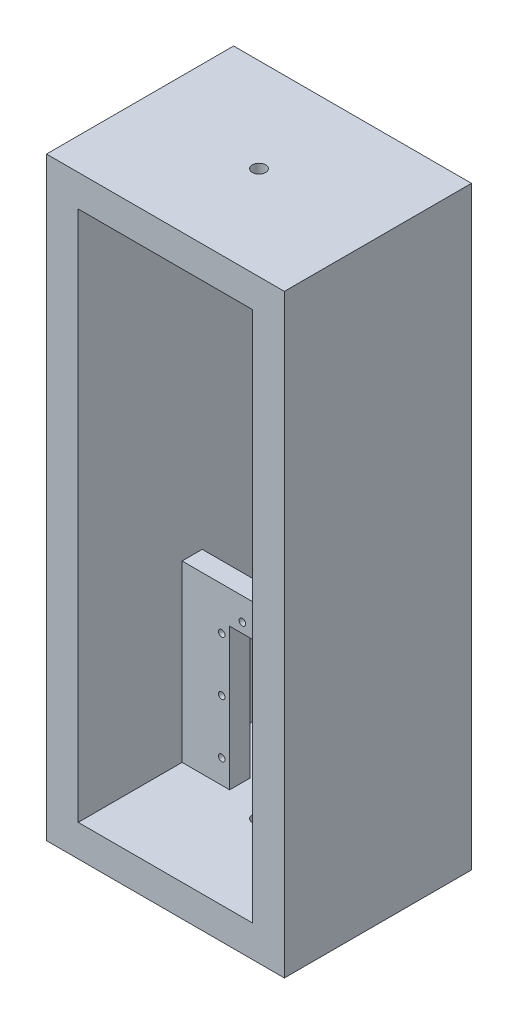
SolidWorks part; units mm, degrees
ref_plane "Front Plane" through (0, 0, 0) normal (0, 0, 1) x (1, 0, 0)
ref_plane "Top Plane" through (0, 0, 0) normal (0, 1, 0) x (1, 0, 0)
ref_plane "Right Plane" through (0, 0, 0) normal (1, 0, 0) x (0, 0, -1)
sketch "Sketch1" plane through (0, 0, 0) normal (0, 0, 1) x (1, 0, 0)
  line L1 (0, 0) -> (75, 0)
  line L2 (0, 0) -> (0, 187.5)
  line L3 (0, 187.5) -> (75, 187.5)
  line L4 (75, 0) -> (75, 187.5)
  line L5 (10, 10) -> (65, 10)
  line L6 (10, 10) -> (10, 177.5)
  line L7 (10, 177.5) -> (65, 177.5)
  line L8 (65, 10) -> (65, 177.5)
  dimension "D1" = 75
  dimension "D2" = 187.5
  dimension "D3" = 10
  dimension "D4" = 10
  dimension "D5" = 10
  dimension "D6" = 10
extrude "Boss-Extrude1" add sketch "Sketch1" against normal blind 59
ref_plane "Plane1" through (0, 0, -37.5) normal (0, 0, 1) x (1, 0, 0)
hole_wizard "Tap Drill for M5x0.8 Tap2" positions "Sketch8" profile "Sketch9" hole size "M5x0.8" standard "ANSI Metric" end condition through all
sketch "Sketch8" plane through (0, 10, 0) normal (0, 1, 0) x (1, 0, 0)
  line L0 (37.5, 59) -> (37.5, 0) construction
  line L1 (10, 59) -> (65, 59) construction
  line L2 (10, 0) -> (65, 0) construction
  point P0 (37.5, 29.5)
sketch "Sketch9" plane through (37.5, 10, -29.5) normal (1, 0, 0) x (0, 0, 1)
  line L0 (0, 0) -> (0, 10)
  line L1 (0, 10) -> (2.1, 10)
  line L2 (2.1, 10) -> (2.1, 0)
  line L5 (2.1, 0) -> (0, 0)
  line L11 (0, -6.35) -> (0, 107.95) construction
  dimension "Thru Hole Dia." = 4.2
  dimension "Thru Hole Depth" = 10
hole_wizard "Tap Drill for M5x0.8 Tap3" positions "Sketch11" profile "Sketch12" hole size "M5x0.8" standard "ANSI Metric"
sketch "Sketch11" plane through (0, 187.5, 0) normal (0, 1, 0) x (1, 0, 0)
  line L0 (0, 29.5) -> (75, 29.5) construction
  line L1 (0, 59) -> (0, 0) construction
  line L2 (75, 59) -> (75, 0) construction
  point P0 (37.5, 29.5)
sketch "Sketch12" plane through (37.5, 187.5, -29.5) normal (1, 0, 0) x (0, 0, 1)
  line L0 (0, 0) -> (0, 11.2618)
  line L1 (0, 11.2618) -> (2.1, 10)
  line L2 (2.1, 10) -> (2.1, 0)
  line L5 (2.1, 0) -> (0, 0)
  line L10 (0, 11.2618) -> (-2.1, 10) construction
  line L11 (0, -6.35) -> (0, 107.95) construction
  dimension "Hole Dia." = 4.2
  dimension "Hole Depth" = 10
  dimension "Drill Angle" = 118
sketch "Sketch13" plane through (0, 10, 0) normal (0, 1, 0) x (1, 0, 0)
  line L0 (65, 59) -> (65, 0) construction
  line L1 (65, 32.75) -> (50, 32.75)
  line L2 (65, 32.75) -> (65, 39.1)
  line L3 (65, 39.1) -> (50, 39.1)
  line L4 (50, 32.75) -> (50, 39.1)
  line L5 (37.5, 59) -> (37.5, 0) construction
  line L6 (10, 59) -> (65, 59) construction
  line L7 (10, 0) -> (65, 0) construction
  line L8 (10, 39.1) -> (25, 39.1)
  line L9 (25, 32.75) -> (25, 39.1)
  line L10 (10, 32.75) -> (25, 32.75)
  line L11 (10, 32.75) -> (10, 39.1)
  dimension "D1" = 26.25
  dimension "D2" = 12.5
  dimension "D3" = 6.35
extrude "Boss-Extrude2" add sketch "Sketch13" along normal blind 55
sketch "Sketch14" plane through (50, 0, 0) normal (-1, 0, 0) x (0, 0, 1)
  line L0 (-32.75, 65) -> (-32.75, 10) construction
  line L1 (-39.1, 65) -> (-32.75, 65)
  line L2 (-39.1, 65) -> (-39.1, 54.7)
  line L3 (-39.1, 54.7) -> (-32.75, 54.7)
  line L4 (-32.75, 65) -> (-32.75, 54.7)
  dimension "D1" = 10.3
extrude "Boss-Extrude3" add sketch "Sketch14" along normal up to surface (25 mm away) contours L1 L4 L3 L2 up to face at (25, 37.5, -35.925)
sketch "Sketch17" plane through (0, 0, -39.1) normal (0, 0, -1) x (-1, 0, 0)
  line L0 (-37.5, 65) -> (-37.5, 10) construction
  line L1 (-65, 65) -> (-10, 65) construction
  line L2 (-10, 10) -> (-65, 10) construction
  line L3 (-22.5, 65) -> (-22.5, 10) construction
  line L5 (-25, 10) -> (-10, 10) construction
  line L6 (-29, 65) -> (-29, 10) construction
  line L8 (-65, 17.5) -> (-10, 17.5) construction
  line L9 (-65, 10) -> (-65, 177.5) construction
  line L10 (-10, 65) -> (-10, 10) construction
  line L11 (-65, 34.5) -> (-10, 34.5) construction
  line L12 (-65, 51.5) -> (-10, 51.5) construction
  line L13 (-65, 57.8) -> (-10, 57.8) construction
  line L14 (-52.5, 65) -> (-52.5, 10) construction
  line L15 (-46, 65) -> (-46, 10) construction
  dimension "D1" = 15
  dimension "D2" = 6.5
  dimension "D3" = 7.5
  dimension "D4" = 17
  dimension "D5" = 17
  dimension "D6" = 6.3
hole_wizard "Tap Drill for M2.5x0.45 Tap1" positions "Sketch18" profile "Sketch19" hole size "M2.5x0.45" standard "ANSI Metric" end condition through all
sketch "Sketch18" plane through (0, 0, -39.1) normal (0, 0, -1) x (-1, 0, 0)
  line L0 (-65, 57.8) -> (-10, 57.8) construction
  line L1 (-46, 65) -> (-46, 10) construction
  line L2 (-29, 65) -> (-29, 10) construction
  line L3 (-22.5, 65) -> (-22.5, 10) construction
  line L4 (-65, 51.5) -> (-10, 51.5) construction
  line L5 (-52.5, 65) -> (-52.5, 10) construction
  line L6 (-65, 34.5) -> (-10, 34.5) construction
  line L7 (-65, 17.5) -> (-10, 17.5) construction
  point P0 (-46, 57.8)
  point P2 (-52.5, 51.5)
  point P4 (-52.5, 34.5)
  point P6 (-52.5, 17.5)
  point P8 (-22.5, 17.5)
  point P10 (-22.5, 34.5)
  point P12 (-22.5, 51.5)
  point P14 (-29, 57.8)
  point P17 (-46, 57.8)
  point P22 (-29, 57.8)
  point P25 (-22.5, 51.5)
  point P30 (-52.5, 51.5)
  point P33 (-52.5, 34.5)
  point P36 (-52.5, 17.5)
  point P39 (-22.5, 17.5)
  point P40 (0, 0)
  point P41 (-22.5, 34.5)
  point P42 (-22.5, 33.5574)
  point P43 (-22.5, 34.5)
sketch "Sketch19" plane through (46, 57.8, -39.1) normal (1, 0, 0) x (0, 1, 0)
  line L0 (0, 0) -> (0, 39.1)
  line L1 (0, 39.1) -> (1.025, 39.1)
  line L2 (1.025, 39.1) -> (1.025, 0)
  line L5 (1.025, 0) -> (0, 0)
  line L11 (0, -6.35) -> (0, 107.95) construction
  dimension "Thru Hole Dia." = 2.05
  dimension "Thru Hole Depth" = 39.1
